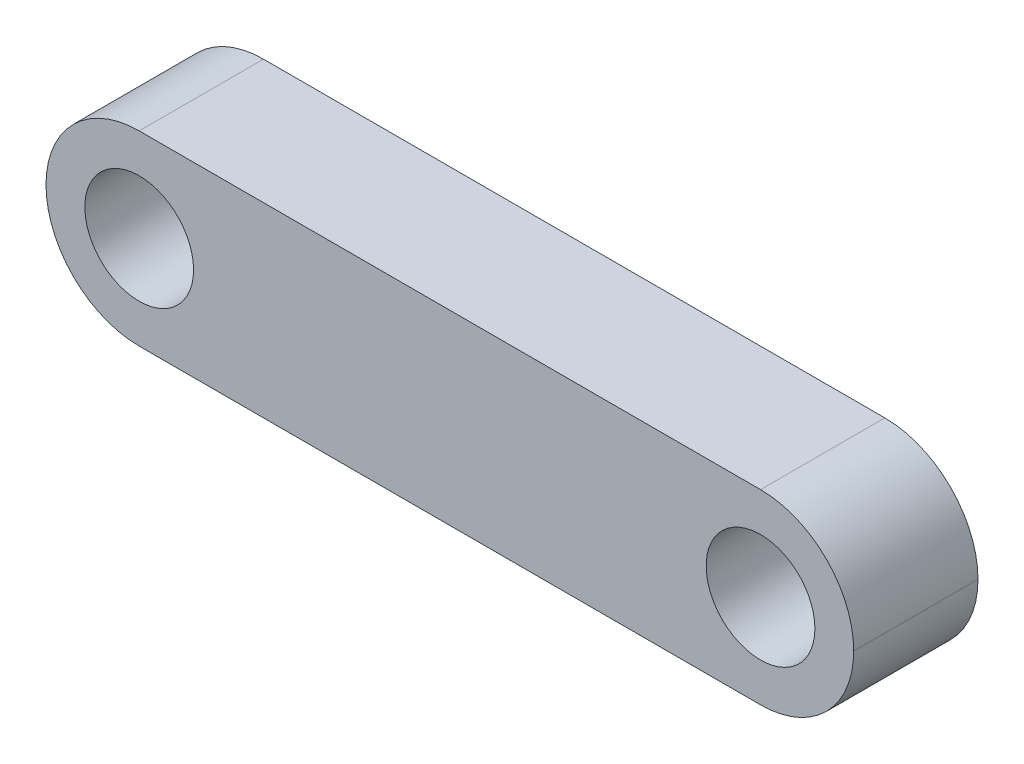
SolidWorks part; units mm, degrees
ref_plane "Alzado" through (0, 0, 0) normal (0, 0, 1) x (1, 0, 0)
ref_plane "Planta" through (0, 0, 0) normal (0, 1, 0) x (1, 0, 0)
ref_plane "Vista lateral" through (0, 0, 0) normal (1, 0, 0) x (0, 0, -1)
sketch "Croquis1" plane through (0, 0, 0) normal (0, 0, 1) x (1, 0, 0)
  line L0 (-21.31, 5.8249) -> (-21.31, -0.1751)
  line L1 (4.69, -0.1751) -> (-21.31, -0.1751)
  line L3 (4.69, 5.8249) -> (-21.31, 5.8249)
  line L5 (4.69, 5.8249) -> (4.69, -0.1751)
  circle A0 centre (1.69, 2.8249) radius 1.75
  circle A1 centre (-18.31, 2.8249) radius 1.75
  dimension "D3" = 3.5
  dimension "D4" = 3.5
  dimension "D5" = 3
  dimension "D6" = 3
  dimension "D7" = 3
  dimension "D8" = 3
  dimension "D1" = 6
  dimension "D2" = 20
extrude "Saliente-Extruir1" add sketch "Croquis1" along normal blind 4
fillet "Redondeo2" radius 3 4 edges at (4.69, 5.8249, 2) (4.69, -0.1751, 2) (-21.31, 5.8249, 2) (-21.31, -0.1751, 2)
